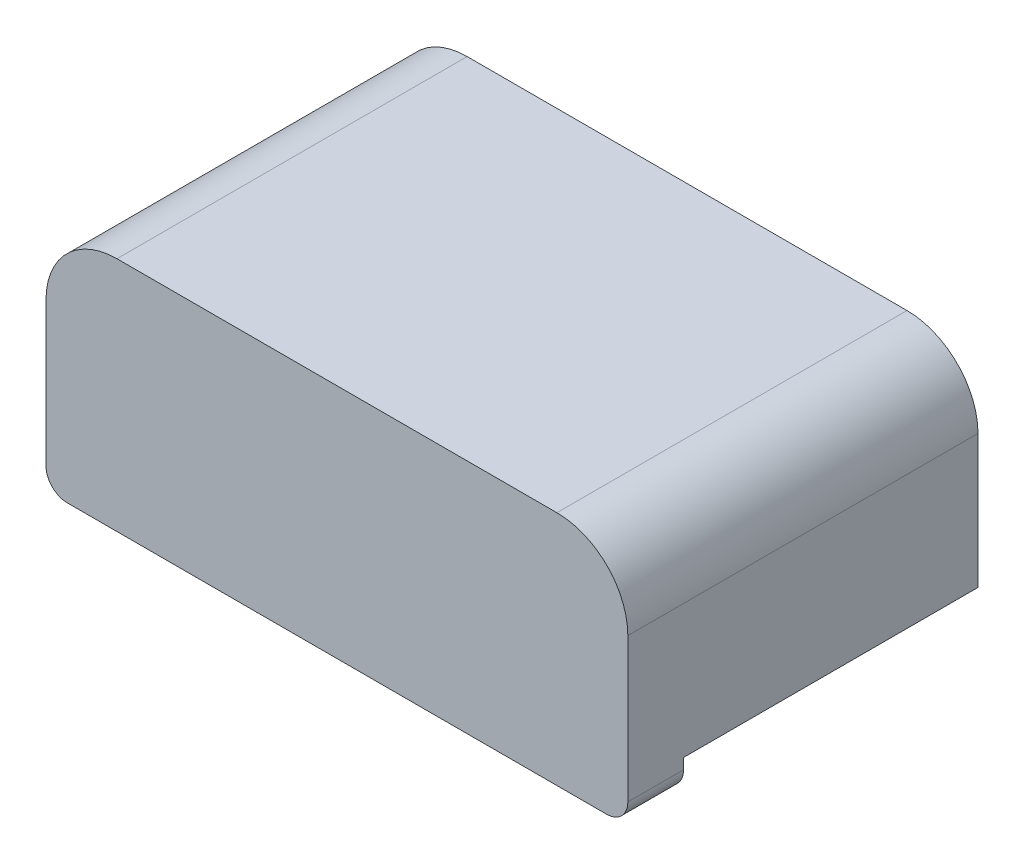
SolidWorks part; units mm, degrees
ref_plane "Front Plane" through (0, 0, 0) normal (0, 0, 1) x (1, 0, 0)
ref_plane "Top Plane" through (0, 0, 0) normal (0, 1, 0) x (1, 0, 0)
ref_plane "Right Plane" through (0, 0, 0) normal (1, 0, 0) x (0, 0, -1)
sketch "Sketch1" plane through (0, 0, 0) normal (0, 0, 1) x (1, 0, 0)
  line L0 (0, -0.45) -> (0, 0) construction
  line L1 (-4.1, -0.45) -> (4.1, -0.45)
  line L2 (-4.1, -0.45) -> (-4.1, 2.88)
  line L3 (-4.1, 2.88) -> (4.1, 2.88)
  line L4 (4.1, -0.45) -> (4.1, 2.88)
  dimension "D1" = 0.45
  dimension "D2" = 8.2
  dimension "D3" = 2.88
extrude "Boss-Extrude1" add sketch "Sketch1" along normal blind 0.785
sketch "Sketch2" plane through (0, 0, 0) normal (0, 0, -1) x (-1, 0, 0)
  line L0 (4.1, 2.88) -> (4.1, -0.45) construction
  line L1 (-4.1, 2.88) -> (4.1, 2.88)
  line L2 (-4.1, 2.88) -> (-4.1, 0)
  line L3 (-4.1, 0) -> (4.1, 0)
  line L4 (4.1, 2.88) -> (4.1, 0)
extrude "Boss-Extrude2" add sketch "Sketch2" along normal offset from surface (4.15 mm away) 4.935 up to face at (0, 1.215, 0.785)
fillet "Fillet1" radius 1 2 edges at (4.1, 2.88, -1.6825) (-4.1, 2.88, -1.6825)
fillet "Fillet2" radius 0.3 2 edges at (4.1, -0.45, 0.3925) (-4.1, -0.45, 0.3925)
sketch "Sketch3" plane through (0, 0, 0) normal (0, -1, 0) x (1, 0, 0)
  line L0 (4.1, 0) -> (-4.1, 0) construction
  line L1 (1.5, -3) -> (3.5, -3)
  line L2 (1.5, -3) -> (1.5, 0)
  line L3 (1.5, 0) -> (3.5, 0)
  line L4 (3.5, -3) -> (3.5, 0)
  line L5 (1.5, -3) -> (3.5, 0) construction
  line L6 (1.5, 0) -> (3.5, -3) construction
  line L7 (-3.5, -3) -> (-1.5, -3)
  line L8 (-3.5, -3) -> (-3.5, 0)
  line L9 (-3.5, 0) -> (-1.5, 0)
  line L10 (-1.5, -3) -> (-1.5, 0)
  line L11 (-3.5, -3) -> (-1.5, 0) construction
  line L12 (-3.5, 0) -> (-1.5, -3) construction
  line L13 (2.5, -1.5) -> (-2.5, -1.5) construction
  point P0 (2.5, -1.5)
  point P5 (-2.5, -1.5)
  point P14 (0, -1.5)
  dimension "D1" = 3
  dimension "D2" = 2
  dimension "D3" = 3
extrude "Boss-Extrude3" add sketch "Sketch3" along normal up to surface (0.45 mm away) up to face at (0, -0.45, 0.3925)
